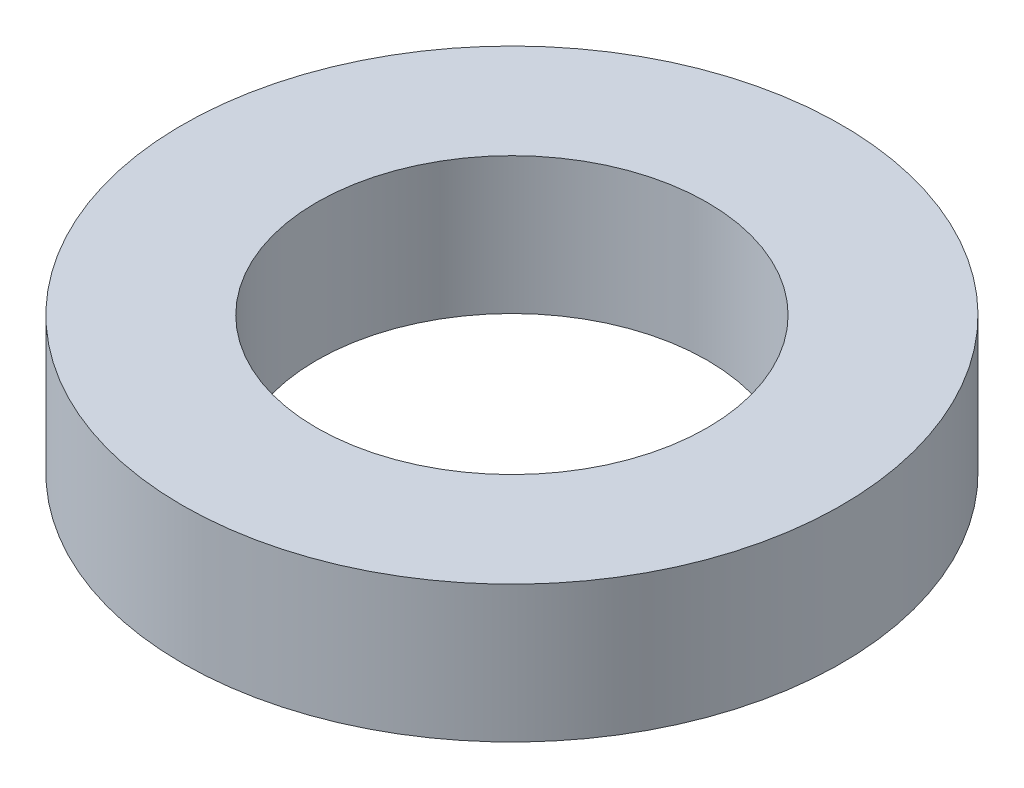
SolidWorks part; units mm, degrees
ref_plane "Front Plane" through (0, 0, 0) normal (0, 0, 1) x (1, 0, 0)
ref_plane "Top Plane" through (0, 0, 0) normal (0, 1, 0) x (1, 0, 0)
ref_plane "Right Plane" through (0, 0, 0) normal (1, 0, 0) x (0, 0, -1)
sketch "Sketch1" plane through (0, 0, 0) normal (0, 1, 0) x (1, 0, 0)
  circle A0 centre (0, 0) radius 67.5
  dimension "FLANGE_OD" = 135
extrude "Boss-Extrude1" add sketch "Sketch1" along normal blind 28
sketch "Sketch2" plane through (0, 0, 0) normal (0, 1, 0) x (1, 0, 0)
  circle A0 centre (0, 0) radius 40
  dimension "BORE_D" = 80
extrude "Cut-Extrude1" cut sketch "Sketch2" along normal through all
sketch "Sketch3" plane through (0, 28, 0) normal (0, 1, 0) x (1, 0, 0)
  circle A0 centre (0, 0) radius 24.4377 construction
  circle A1 centre (-24.4377, 0) radius 4.0269
  dimension "BOLT_D" = 8.0538
  dimension "BOLT_PCD" = 48.8754
extrude "Cut-Extrude2" cut sketch "Sketch3" against normal blind 17.7693 rebuild error yes
pattern_circular "CirPattern1" count 3 over 360 rebuild error yes
